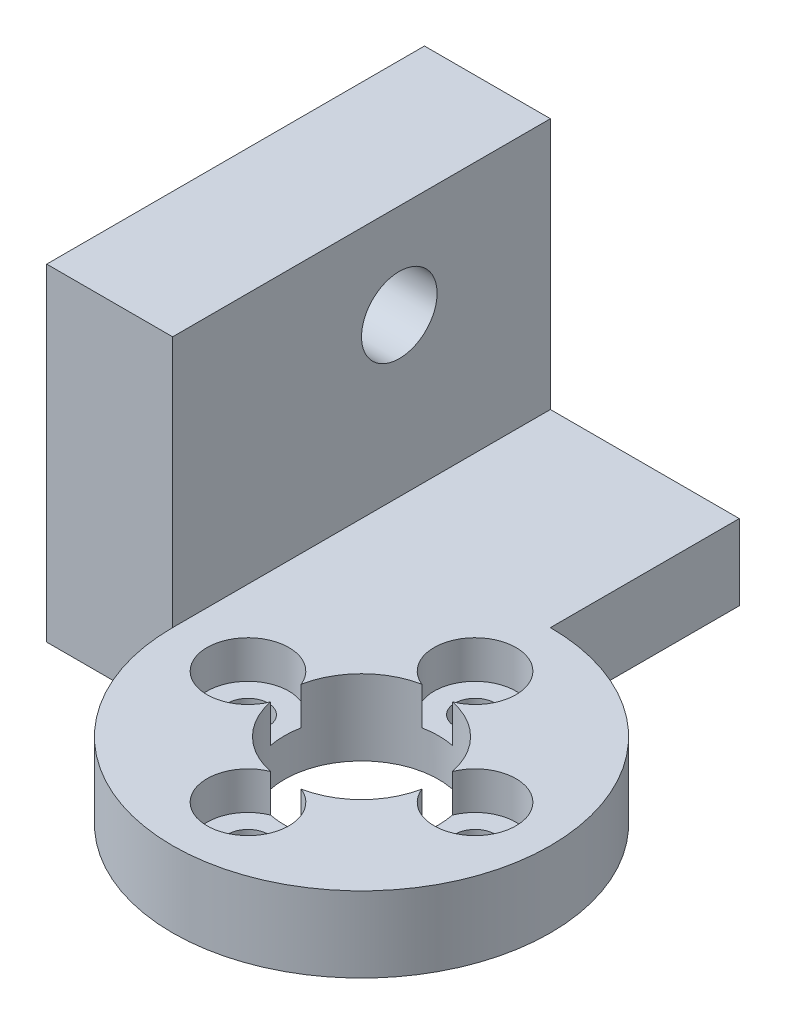
SolidWorks part; units mm, degrees
ref_plane "Front Plane" through (0, 0, 0) normal (0, 0, 1) x (1, 0, 0)
ref_plane "Top Plane" through (0, 0, 0) normal (0, 1, 0) x (1, 0, 0)
ref_plane "Right Plane" through (0, 0, 0) normal (1, 0, 0) x (0, 0, -1)
sketch "Sketch1" plane through (0, 0, 0) normal (0, 1, 0) x (1, 0, 0)
  circle A0 centre (0, 0) radius 15
  dimension "D1" = 30
extrude "Boss-Extrude1" add sketch "Sketch1" along normal blind 6
sketch "Sketch2" plane through (0, 6, 0) normal (0, 1, 0) x (1, 0, 0)
  circle A0 centre (0, 0) radius 6.125
  dimension "D1" = 12.25
extrude "Cut-Extrude1" cut sketch "Sketch2" against normal up to next
hole_wizard "CBORE for M3 SHCS2" positions "Sketch3" profile "Sketch5" counterbore size "M3" standard "ANSI Metric" end condition up to next
sketch "Sketch3" plane through (0, 6, 0) normal (0, 1, 0) x (1, 0, 0)
  point P0 (0, 9.017)
  dimension "D1" = 9.017
sketch "Sketch5" plane through (0, 6, -9.017) normal (1, 0, 0) x (0, 0, 1)
  line L0 (0, 0) -> (0, 6)
  line L1 (0, 6) -> (1.6, 6)
  line L3 (1.6, 6) -> (1.6, 3)
  line L4 (1.6, 3) -> (3.25, 3)
  line L5 (3.25, 3) -> (3.25, 0)
  line L7 (3.25, 0) -> (0, 0)
  line L11 (0, -6.35) -> (0, 107.95) construction
  dimension "Thru Hole Dia." = 3.2
  dimension "Thru Hole Depth" = 6
  dimension "C'Bore Dia." = 6.5
  dimension "C'Bore Depth" = 3
pattern_circular "CirPattern1" count 4 over 360 about axis through (0, -0.001, 0) along (0, 1, 0) of "CBORE for M3 SHCS2"
sketch "Sketch6" plane through (0, 6, 0) normal (0, 1, 0) x (1, 0, 0)
  line L0 (-25, 0) -> (-25, 15)
  line L1 (-25, 15) -> (0, 15)
  line L2 (-25, 0) -> (-15, 0)
  circle A0 centre (0, 0) radius 15 construction
  arc A1 (0, 15) -> (-15, 0) centre (0, 0) ccw
  point P6 (-2.5495, 14.7817)
  dimension "D1" = 25
extrude "Boss-Extrude2" add sketch "Sketch6" against normal up to surface (6 mm away) and the other way blind 20 up to face at (9.017, 0, 1.6)
sketch "Sketch7" plane through (-25, 0, 0) normal (-1, 0, 0) x (0, 0, 1)
  line L4 (-15, 6) -> (0, 6)
  line L5 (-15, 26) -> (-15, 6)
  line L6 (0, 26) -> (-15, 26)
  line L7 (0, 6) -> (0, 26)
  line L8 (-15, 6) -> (0, 6)
  line L9 (-15, 26) -> (-15, 6)
  line L10 (0, 26) -> (-15, 26)
  line L11 (0, 6) -> (0, 26)
  dimension "D1" = 0
extrude "Cut-Extrude2" cut sketch "Sketch7" against normal up to next from vertex starting at point (-15, 26, 0)
sketch "Sketch9" plane through (0, 0, -15) normal (0, 0, -1) x (-1, 0, 0)
  line L6 (15, 26) -> (15, 6)
  line L7 (15, 6) -> (0, 6)
  line L8 (0, 6) -> (0, 0)
  line L9 (0, 0) -> (25, 0)
  line L10 (25, 0) -> (25, 26)
  line L11 (25, 26) -> (15, 26)
  line L12 (15, 26) -> (15, 6)
  line L13 (15, 6) -> (0, 6)
  line L14 (0, 6) -> (0, 0)
  line L15 (0, 0) -> (25, 0)
  line L16 (25, 0) -> (25, 26)
  line L17 (25, 26) -> (15, 26)
  dimension "D1" = 0
extrude "Boss-Extrude3" add sketch "Sketch9" along normal blind 15
sketch "Sketch8" plane through (-15, 0, 0) normal (1, 0, 0) x (0, 0, -1)
  line L0 (0, 0) -> (0, 37.894) construction
  line L1 (8, 0) -> (8, 37.894) construction
  line L2 (-15, 0) -> (15, 0) construction
  line L3 (18, 0) -> (18, 37.894) construction
  line L4 (30, 6) -> (15, 6) construction
  circle A0 centre (18, 18.5) radius 10 construction
  circle A1 centre (18, 18.5) radius 3
  dimension "D3" = 12.5
  dimension "D4" = 6
  dimension "D1" = 8
  dimension "D2" = 10
extrude "Cut-Extrude3" cut sketch "Sketch8" against normal up to next
